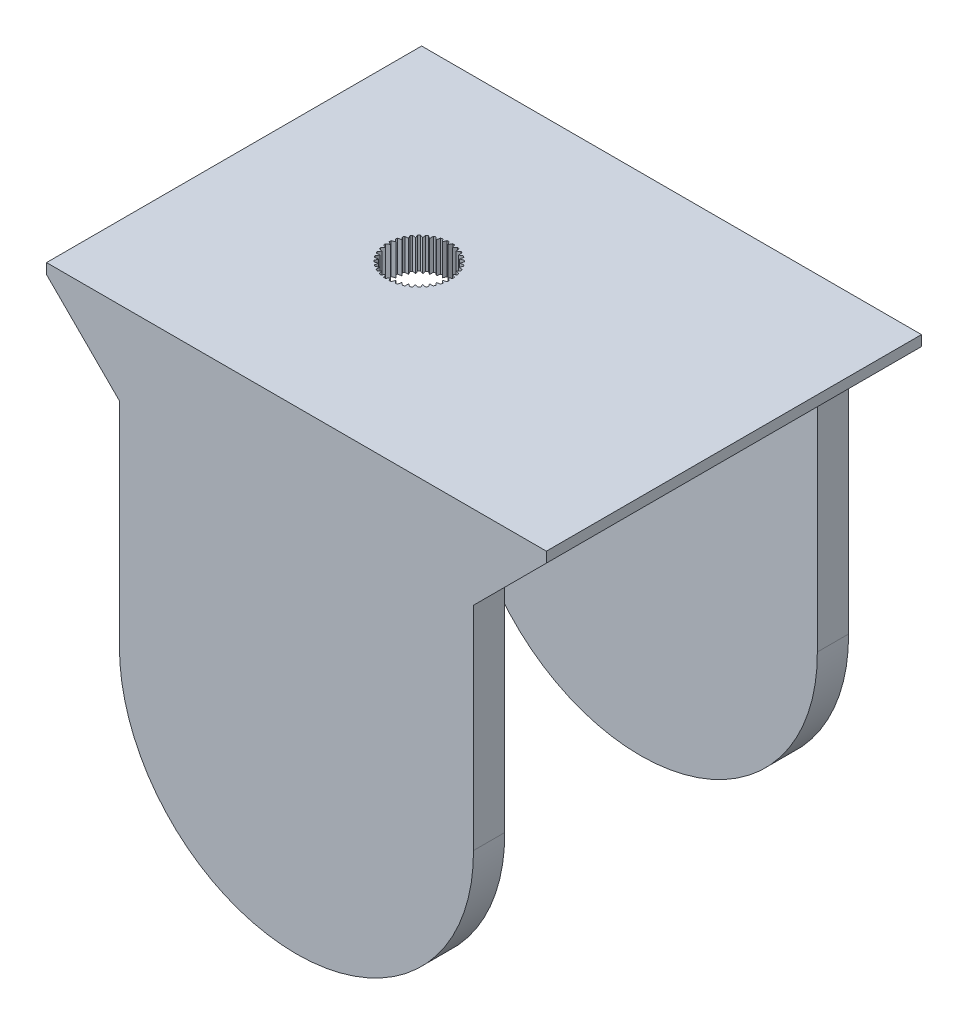
SolidWorks part; units mm, degrees
ref_plane "Front Plane" through (0, 0, 0) normal (0, 0, 1) x (1, 0, 0)
ref_plane "Top Plane" through (0, 0, 0) normal (0, 1, 0) x (1, 0, 0)
ref_plane "Right Plane" through (0, 0, 0) normal (1, 0, 0) x (0, 0, -1)
sketch "Sketch1" plane through (0, 0, 0) normal (0, 1, 0) x (1, 0, 0)
  line L1 (-24, -18.01) -> (24, -18.01)
  line L2 (-24, -18.01) -> (-24, 18.01)
  line L3 (-24, 18.01) -> (24, 18.01)
  line L4 (24, -18.01) -> (24, 18.01)
  point P4 (0, 18.01)
  point P6 (-24, 0)
  dimension "D1" = 48
  dimension "D2" = 36.02
extrude "Boss-Extrude1" add sketch "Sketch1" along normal blind 3
sketch "Sketch2" plane through (0, 3, 0) normal (0, 1, 0) x (1, 0, 0)
  line L0 (2.3718, 1.5412) -> (2.4182, 1.6214) construction
  line L1 (2.3507, 1.7178) -> (2.2594, 1.7017) construction
  line L2 (2.4182, 1.6214) -> (2.4507, 1.6778) construction
  line L3 (2.4148, 1.7291) -> (2.3507, 1.7178) construction
  line L4 (2.2919, 1.4028) -> (2.3718, 1.5412) construction
  line L5 (2.2594, 1.7017) -> (2.1021, 1.6739) construction
  line L6 (2.0999, 2.0167) -> (2.1221, 2.0778) construction
  line L7 (2.0778, 2.1221) -> (2.0167, 2.0999) construction
  line L8 (2.0682, 1.9296) -> (2.0999, 2.0167) construction
  line L9 (2.0167, 2.0999) -> (1.9296, 2.0682) construction
  line L10 (2.0135, 1.7795) -> (2.0682, 1.9296) construction
  line L11 (1.9296, 2.0682) -> (1.7795, 2.0135) construction
  line L12 (1.6778, 2.4507) -> (1.6214, 2.4182) construction
  line L13 (1.7178, 2.3507) -> (1.7291, 2.4148) construction
  line L14 (1.6214, 2.4182) -> (1.5412, 2.3718) construction
  line L15 (1.7017, 2.2594) -> (1.7178, 2.3507) construction
  line L16 (1.5412, 2.3718) -> (1.4028, 2.2919) construction
  line L17 (1.6739, 2.1021) -> (1.7017, 2.2594) construction
  line L18 (2.5007, 0.9835) -> (2.6034, 1.1059) construction
  line L19 (2.5206, 1.2835) -> (2.3608, 1.2835) construction
  line L20 (2.663, 1.1768) -> (2.7048, 1.2267) construction
  line L21 (2.6783, 1.2835) -> (2.6132, 1.2835) construction
  line L22 (2.6034, 1.1059) -> (2.663, 1.1768) construction
  line L23 (2.6132, 1.2835) -> (2.5206, 1.2835) construction
  line L24 (2.8269, 0.6965) -> (2.8767, 0.7384) construction
  line L25 (2.8605, 0.7989) -> (2.7964, 0.8102) construction
  line L26 (2.7559, 0.637) -> (2.8269, 0.6965) construction
  line L27 (2.7964, 0.8102) -> (2.7052, 0.8263) construction
  line L28 (2.6335, 0.5343) -> (2.7559, 0.637) construction
  line L29 (2.7052, 0.8263) -> (2.5478, 0.854) construction
  line L30 (2.6863, 0.0689) -> (2.8247, 0.1488) construction
  line L31 (2.8076, 0.344) -> (2.6574, 0.3986) construction
  line L32 (2.8247, 0.1488) -> (2.9049, 0.1951) construction
  line L33 (2.8946, 0.3123) -> (2.8076, 0.344) construction
  line L34 (2.9049, 0.1951) -> (2.9613, 0.2276) construction
  line L35 (2.9558, 0.29) -> (2.8946, 0.3123) construction
  line L36 (2.9613, -0.2276) -> (2.9049, -0.1951) construction
  line L37 (2.8946, -0.3123) -> (2.9558, -0.29) construction
  line L38 (2.9049, -0.1951) -> (2.8247, -0.1488) construction
  line L39 (2.8076, -0.344) -> (2.8946, -0.3123) construction
  line L40 (2.8247, -0.1488) -> (2.6863, -0.0689) construction
  line L41 (2.6574, -0.3986) -> (2.8076, -0.344) construction
  line L42 (2.7964, -0.8102) -> (2.8605, -0.7989) construction
  line L43 (2.8767, -0.7384) -> (2.8269, -0.6965) construction
  line L44 (2.7052, -0.8263) -> (2.7964, -0.8102) construction
  line L45 (2.8269, -0.6965) -> (2.7559, -0.637) construction
  line L46 (2.5478, -0.854) -> (2.7052, -0.8263) construction
  line L47 (2.7559, -0.637) -> (2.6335, -0.5343) construction
  line L48 (2.5206, -1.2835) -> (2.6132, -1.2835) construction
  line L49 (2.663, -1.1768) -> (2.6034, -1.1059) construction
  line L50 (2.3608, -1.2835) -> (2.5206, -1.2835) construction
  line L51 (2.6034, -1.1059) -> (2.5007, -0.9835) construction
  line L52 (2.6863, -0.0689) -> (2.567, 0) construction
  line L53 (2.567, 0) -> (2.6863, 0.0689) construction
  line L54 (2.6574, 0.3986) -> (2.528, 0.4458) construction
  line L55 (2.528, 0.4458) -> (2.6335, 0.5343) construction
  line L56 (2.5478, 0.854) -> (2.4122, 0.878) construction
  line L57 (2.4122, 0.878) -> (2.5007, 0.9835) construction
  line L58 (2.3608, 1.2835) -> (2.2231, 1.2835) construction
  line L59 (2.2231, 1.2835) -> (2.2919, 1.4028) construction
  line L60 (2.1021, 1.6739) -> (1.9664, 1.65) construction
  line L61 (1.9664, 1.65) -> (2.0135, 1.7795) construction
  line L62 (1.7795, 2.0135) -> (1.65, 1.9664) construction
  line L63 (1.65, 1.9664) -> (1.6739, 2.1021) construction
  line L64 (1.4028, 2.2919) -> (1.2835, 2.2231) construction
  line L65 (1.2835, 2.2231) -> (1.2835, 2.3608) construction
  line L66 (0.9835, 2.5007) -> (0.878, 2.4122) construction
  line L67 (0.878, 2.4122) -> (0.854, 2.5478) construction
  line L68 (0.5343, 2.6335) -> (0.4458, 2.528) construction
  line L69 (0.4458, 2.528) -> (0.3986, 2.6574) construction
  line L70 (0.0689, 2.6863) -> (0, 2.567) construction
  line L71 (0, 2.567) -> (-0.0689, 2.6863) construction
  line L72 (-0.3986, 2.6574) -> (-0.4458, 2.528) construction
  line L73 (-0.4458, 2.528) -> (-0.5343, 2.6335) construction
  line L74 (-0.854, 2.5478) -> (-0.878, 2.4122) construction
  line L75 (-0.878, 2.4122) -> (-0.9835, 2.5007) construction
  line L76 (-1.2835, 2.3608) -> (-1.2835, 2.2231) construction
  line L77 (-1.2835, 2.2231) -> (-1.4028, 2.2919) construction
  line L78 (-1.6739, 2.1021) -> (-1.65, 1.9664) construction
  line L79 (-1.65, 1.9664) -> (-1.7795, 2.0135) construction
  line L80 (-2.0135, 1.7795) -> (-1.9664, 1.65) construction
  line L81 (-1.9664, 1.65) -> (-2.1021, 1.6739) construction
  line L82 (-2.2919, 1.4028) -> (-2.2231, 1.2835) construction
  line L83 (-2.2231, 1.2835) -> (-2.3608, 1.2835) construction
  line L84 (-2.5007, 0.9835) -> (-2.4122, 0.878) construction
  line L85 (-2.4122, 0.878) -> (-2.5478, 0.854) construction
  line L86 (-2.6335, 0.5343) -> (-2.528, 0.4458) construction
  line L87 (-2.528, 0.4458) -> (-2.6574, 0.3986) construction
  line L88 (-2.6863, 0.0689) -> (-2.567, 0) construction
  line L89 (-2.567, 0) -> (-2.6863, -0.0689) construction
  line L90 (-2.6574, -0.3986) -> (-2.528, -0.4458) construction
  line L91 (-2.528, -0.4458) -> (-2.6335, -0.5343) construction
  line L92 (-2.5478, -0.854) -> (-2.4122, -0.878) construction
  line L93 (-2.4122, -0.878) -> (-2.5007, -0.9835) construction
  line L94 (-2.3608, -1.2835) -> (-2.2231, -1.2835) construction
  line L95 (-2.2231, -1.2835) -> (-2.2919, -1.4028) construction
  line L96 (-2.1021, -1.6739) -> (-1.9664, -1.65) construction
  line L97 (-1.9664, -1.65) -> (-2.0135, -1.7795) construction
  line L98 (-1.7795, -2.0135) -> (-1.65, -1.9664) construction
  line L99 (-1.65, -1.9664) -> (-1.6739, -2.1021) construction
  line L100 (-1.4028, -2.2919) -> (-1.2835, -2.2231) construction
  line L101 (-1.2835, -2.2231) -> (-1.2835, -2.3608) construction
  line L102 (-0.9835, -2.5007) -> (-0.878, -2.4122) construction
  line L103 (-0.878, -2.4122) -> (-0.854, -2.5478) construction
  line L104 (-0.5343, -2.6335) -> (-0.4458, -2.528) construction
  line L105 (-0.4458, -2.528) -> (-0.3986, -2.6574) construction
  line L106 (-0.0689, -2.6863) -> (0, -2.567) construction
  line L107 (0, -2.567) -> (0.0689, -2.6863) construction
  line L108 (0.3986, -2.6574) -> (0.4458, -2.528) construction
  line L109 (0.4458, -2.528) -> (0.5343, -2.6335) construction
  line L110 (0.854, -2.5478) -> (0.878, -2.4122) construction
  line L111 (0.878, -2.4122) -> (0.9835, -2.5007) construction
  line L112 (1.2835, -2.3608) -> (1.2835, -2.2231) construction
  line L113 (1.2835, -2.2231) -> (1.4028, -2.2919) construction
  line L114 (1.6739, -2.1021) -> (1.65, -1.9664) construction
  line L115 (1.65, -1.9664) -> (1.7795, -2.0135) construction
  line L116 (2.0135, -1.7795) -> (1.9664, -1.65) construction
  line L117 (1.9664, -1.65) -> (2.1021, -1.6739) construction
  line L118 (2.2919, -1.4028) -> (2.2231, -1.2835) construction
  line L119 (2.2231, -1.2835) -> (2.3608, -1.2835) construction
  line L120 (2.5007, -0.9835) -> (2.4122, -0.878) construction
  line L121 (2.4122, -0.878) -> (2.5478, -0.854) construction
  line L122 (2.6335, -0.5343) -> (2.528, -0.4458) construction
  line L123 (2.528, -0.4458) -> (2.6574, -0.3986) construction
  line L124 (2.6132, -1.2835) -> (2.6783, -1.2835) construction
  line L125 (2.7048, -1.2267) -> (2.663, -1.1768) construction
  line L126 (2.4507, -1.6778) -> (2.4182, -1.6214) construction
  line L127 (2.3507, -1.7178) -> (2.4148, -1.7291) construction
  line L128 (2.4182, -1.6214) -> (2.3718, -1.5412) construction
  line L129 (2.2594, -1.7017) -> (2.3507, -1.7178) construction
  line L130 (1.7795, -2.0135) -> (1.9296, -2.0682) construction
  line L131 (2.0682, -1.9296) -> (2.0135, -1.7795) construction
  line L132 (1.9296, -2.0682) -> (2.0167, -2.0999) construction
  line L133 (2.0999, -2.0167) -> (2.0682, -1.9296) construction
  line L134 (2.0167, -2.0999) -> (2.0778, -2.1221) construction
  line L135 (2.1221, -2.0778) -> (2.0999, -2.0167) construction
  line L136 (2.3718, -1.5412) -> (2.2919, -1.4028) construction
  line L137 (2.1021, -1.6739) -> (2.2594, -1.7017) construction
  line L138 (1.7291, -2.4148) -> (1.7178, -2.3507) construction
  line L139 (1.6214, -2.4182) -> (1.6778, -2.4507) construction
  line L140 (1.7178, -2.3507) -> (1.7017, -2.2594) construction
  line L141 (1.5412, -2.3718) -> (1.6214, -2.4182) construction
  line L142 (1.7017, -2.2594) -> (1.6739, -2.1021) construction
  line L143 (1.4028, -2.2919) -> (1.5412, -2.3718) construction
  line L144 (-0.3123, -2.8946) -> (-0.29, -2.9558) construction
  line L145 (-0.2276, -2.9613) -> (-0.1951, -2.9049) construction
  line L146 (-0.344, -2.8076) -> (-0.3123, -2.8946) construction
  line L147 (-0.1951, -2.9049) -> (-0.1488, -2.8247) construction
  line L148 (0.344, -2.8076) -> (0.3986, -2.6574) construction
  line L149 (0.0689, -2.6863) -> (0.1488, -2.8247) construction
  line L150 (0.3123, -2.8946) -> (0.344, -2.8076) construction
  line L151 (0.1488, -2.8247) -> (0.1951, -2.9049) construction
  line L152 (0.29, -2.9558) -> (0.3123, -2.8946) construction
  line L153 (0.1951, -2.9049) -> (0.2276, -2.9613) construction
  line L154 (0.6965, -2.8269) -> (0.7384, -2.8767) construction
  line L155 (0.7989, -2.8605) -> (0.8102, -2.7964) construction
  line L156 (1.1768, -2.663) -> (1.2267, -2.7048) construction
  line L157 (1.2835, -2.6783) -> (1.2835, -2.6132) construction
  line L158 (1.1059, -2.6034) -> (1.1768, -2.663) construction
  line L159 (1.2835, -2.6132) -> (1.2835, -2.5206) construction
  line L160 (0.9835, -2.5007) -> (1.1059, -2.6034) construction
  line L161 (1.2835, -2.5206) -> (1.2835, -2.3608) construction
  line L162 (0.637, -2.7559) -> (0.6965, -2.8269) construction
  line L163 (0.8102, -2.7964) -> (0.8263, -2.7052) construction
  line L164 (0.5343, -2.6335) -> (0.637, -2.7559) construction
  line L165 (0.8263, -2.7052) -> (0.854, -2.5478) construction
  line L166 (-0.3986, -2.6574) -> (-0.344, -2.8076) construction
  line L167 (-0.1488, -2.8247) -> (-0.0689, -2.6863) construction
  line L168 (-0.8102, -2.7964) -> (-0.7989, -2.8605) construction
  line L169 (-0.7384, -2.8767) -> (-0.6965, -2.8269) construction
  line L170 (-0.8263, -2.7052) -> (-0.8102, -2.7964) construction
  line L171 (-0.6965, -2.8269) -> (-0.637, -2.7559) construction
  line L172 (-0.854, -2.5478) -> (-0.8263, -2.7052) construction
  line L173 (-0.637, -2.7559) -> (-0.5343, -2.6335) construction
  line L174 (-1.2835, -2.6132) -> (-1.2835, -2.6783) construction
  line L175 (-1.2267, -2.7048) -> (-1.1768, -2.663) construction
  line L176 (-1.2835, -2.5206) -> (-1.2835, -2.6132) construction
  line L177 (-1.1768, -2.663) -> (-1.1059, -2.6034) construction
  line L178 (-1.2835, -2.3608) -> (-1.2835, -2.5206) construction
  line L179 (-1.1059, -2.6034) -> (-0.9835, -2.5007) construction
  line L180 (-1.7178, -2.3507) -> (-1.7291, -2.4148) construction
  line L181 (-1.6778, -2.4507) -> (-1.6214, -2.4182) construction
  line L182 (-1.7017, -2.2594) -> (-1.7178, -2.3507) construction
  line L183 (-1.6214, -2.4182) -> (-1.5412, -2.3718) construction
  line L184 (-1.6739, -2.1021) -> (-1.7017, -2.2594) construction
  line L185 (-1.5412, -2.3718) -> (-1.4028, -2.2919) construction
  line L186 (-2.0999, -2.0167) -> (-2.1221, -2.0778) construction
  line L187 (-2.0778, -2.1221) -> (-2.0167, -2.0999) construction
  line L188 (-2.0682, -1.9296) -> (-2.0999, -2.0167) construction
  line L189 (-2.0167, -2.0999) -> (-1.9296, -2.0682) construction
  line L190 (-2.0135, -1.7795) -> (-2.0682, -1.9296) construction
  line L191 (-1.9296, -2.0682) -> (-1.7795, -2.0135) construction
  line L192 (-2.4148, -1.7291) -> (-2.3507, -1.7178) construction
  line L193 (-2.4182, -1.6214) -> (-2.4507, -1.6778) construction
  line L194 (-2.3507, -1.7178) -> (-2.2594, -1.7017) construction
  line L195 (-2.3718, -1.5412) -> (-2.4182, -1.6214) construction
  line L196 (-2.2594, -1.7017) -> (-2.1021, -1.6739) construction
  line L197 (-2.2919, -1.4028) -> (-2.3718, -1.5412) construction
  line L198 (-2.6783, -1.2835) -> (-2.6132, -1.2835) construction
  line L199 (-2.663, -1.1768) -> (-2.7048, -1.2267) construction
  line L200 (-2.6132, -1.2835) -> (-2.5206, -1.2835) construction
  line L201 (-2.6034, -1.1059) -> (-2.663, -1.1768) construction
  line L202 (-2.5206, -1.2835) -> (-2.3608, -1.2835) construction
  line L203 (-2.5007, -0.9835) -> (-2.6034, -1.1059) construction
  line L204 (-2.8605, -0.7989) -> (-2.7964, -0.8102) construction
  line L205 (-2.8269, -0.6965) -> (-2.8767, -0.7384) construction
  line L206 (-2.7964, -0.8102) -> (-2.7052, -0.8263) construction
  line L207 (-2.7559, -0.637) -> (-2.8269, -0.6965) construction
  line L208 (-2.7052, -0.8263) -> (-2.5478, -0.854) construction
  line L209 (-2.6335, -0.5343) -> (-2.7559, -0.637) construction
  line L210 (-2.9558, -0.29) -> (-2.8946, -0.3123) construction
  line L211 (-2.9049, -0.1951) -> (-2.9613, -0.2276) construction
  line L212 (-2.8076, -0.344) -> (-2.6574, -0.3986) construction
  line L213 (-2.6863, -0.0689) -> (-2.8247, -0.1488) construction
  line L214 (-2.8946, -0.3123) -> (-2.8076, -0.344) construction
  line L215 (-2.8247, -0.1488) -> (-2.9049, -0.1951) construction
  line L216 (-2.9613, 0.2276) -> (-2.9049, 0.1951) construction
  line L217 (-2.8946, 0.3123) -> (-2.9558, 0.29) construction
  line L218 (-2.9049, 0.1951) -> (-2.8247, 0.1488) construction
  line L219 (-2.8076, 0.344) -> (-2.8946, 0.3123) construction
  line L220 (-2.8247, 0.1488) -> (-2.6863, 0.0689) construction
  line L221 (-2.6574, 0.3986) -> (-2.8076, 0.344) construction
  line L222 (-2.8269, 0.6965) -> (-2.7559, 0.637) construction
  line L223 (-2.7052, 0.8263) -> (-2.7964, 0.8102) construction
  line L224 (-2.8767, 0.7384) -> (-2.8269, 0.6965) construction
  line L225 (-2.7964, 0.8102) -> (-2.8605, 0.7989) construction
  line L226 (-2.7559, 0.637) -> (-2.6335, 0.5343) construction
  line L227 (-2.5478, 0.854) -> (-2.7052, 0.8263) construction
  line L228 (-2.663, 1.1768) -> (-2.6034, 1.1059) construction
  line L229 (-2.5206, 1.2835) -> (-2.6132, 1.2835) construction
  line L230 (-2.7048, 1.2267) -> (-2.663, 1.1768) construction
  line L231 (-2.6132, 1.2835) -> (-2.6783, 1.2835) construction
  line L232 (-2.6034, 1.1059) -> (-2.5007, 0.9835) construction
  line L233 (-2.3608, 1.2835) -> (-2.5206, 1.2835) construction
  line L234 (-2.4507, 1.6778) -> (-2.4182, 1.6214) construction
  line L235 (-2.3507, 1.7178) -> (-2.4148, 1.7291) construction
  line L236 (-2.4182, 1.6214) -> (-2.3718, 1.5412) construction
  line L237 (-2.2594, 1.7017) -> (-2.3507, 1.7178) construction
  line L238 (-2.3718, 1.5412) -> (-2.2919, 1.4028) construction
  line L239 (-2.1021, 1.6739) -> (-2.2594, 1.7017) construction
  line L240 (-2.0167, 2.0999) -> (-2.0778, 2.1221) construction
  line L241 (-2.1221, 2.0778) -> (-2.0999, 2.0167) construction
  line L242 (-1.9296, 2.0682) -> (-2.0167, 2.0999) construction
  line L243 (-2.0999, 2.0167) -> (-2.0682, 1.9296) construction
  line L244 (-1.7795, 2.0135) -> (-1.9296, 2.0682) construction
  line L245 (-2.0682, 1.9296) -> (-2.0135, 1.7795) construction
  line L246 (-1.7291, 2.4148) -> (-1.7178, 2.3507) construction
  line L247 (-1.6214, 2.4182) -> (-1.6778, 2.4507) construction
  line L248 (-1.7178, 2.3507) -> (-1.7017, 2.2594) construction
  line L249 (-1.5412, 2.3718) -> (-1.6214, 2.4182) construction
  line L250 (-1.7017, 2.2594) -> (-1.6739, 2.1021) construction
  line L251 (-1.4028, 2.2919) -> (-1.5412, 2.3718) construction
  line L252 (-1.2835, 2.6783) -> (-1.2835, 2.6132) construction
  line L253 (-1.1768, 2.663) -> (-1.2267, 2.7048) construction
  line L254 (-1.2835, 2.6132) -> (-1.2835, 2.5206) construction
  line L255 (-1.1059, 2.6034) -> (-1.1768, 2.663) construction
  line L256 (-1.2835, 2.5206) -> (-1.2835, 2.3608) construction
  line L257 (-0.9835, 2.5007) -> (-1.1059, 2.6034) construction
  line L258 (-0.7989, 2.8605) -> (-0.8102, 2.7964) construction
  line L259 (-0.6965, 2.8269) -> (-0.7384, 2.8767) construction
  line L260 (-0.8102, 2.7964) -> (-0.8263, 2.7052) construction
  line L261 (-0.637, 2.7559) -> (-0.6965, 2.8269) construction
  line L262 (-0.8263, 2.7052) -> (-0.854, 2.5478) construction
  line L263 (-0.5343, 2.6335) -> (-0.637, 2.7559) construction
  line L264 (1.1768, 2.663) -> (1.1059, 2.6034) construction
  line L265 (1.2835, 2.5206) -> (1.2835, 2.6132) construction
  line L266 (1.2267, 2.7048) -> (1.1768, 2.663) construction
  line L267 (1.2835, 2.6132) -> (1.2835, 2.6783) construction
  line L268 (1.1059, 2.6034) -> (0.9835, 2.5007) construction
  line L269 (1.2835, 2.3608) -> (1.2835, 2.5206) construction
  line L270 (0.8102, 2.7964) -> (0.7989, 2.8605) construction
  line L271 (0.7384, 2.8767) -> (0.6965, 2.8269) construction
  line L272 (0.8263, 2.7052) -> (0.8102, 2.7964) construction
  line L273 (0.6965, 2.8269) -> (0.637, 2.7559) construction
  line L274 (0.854, 2.5478) -> (0.8263, 2.7052) construction
  line L275 (0.637, 2.7559) -> (0.5343, 2.6335) construction
  line L276 (0.3123, 2.8946) -> (0.29, 2.9558) construction
  line L277 (0.2276, 2.9613) -> (0.1951, 2.9049) construction
  line L278 (0.344, 2.8076) -> (0.3123, 2.8946) construction
  line L279 (0.1951, 2.9049) -> (0.1488, 2.8247) construction
  line L280 (0.3986, 2.6574) -> (0.344, 2.8076) construction
  line L281 (0.1488, 2.8247) -> (0.0689, 2.6863) construction
  line L282 (-0.29, 2.9558) -> (-0.3123, 2.8946) construction
  line L283 (-0.1951, 2.9049) -> (-0.2276, 2.9613) construction
  line L284 (-0.3123, 2.8946) -> (-0.344, 2.8076) construction
  line L285 (-0.1488, 2.8247) -> (-0.1951, 2.9049) construction
  line L286 (-0.344, 2.8076) -> (-0.3986, 2.6574) construction
  line L287 (-0.0689, 2.6863) -> (-0.1488, 2.8247) construction
  line L288 (2.4584, 1.4912) -> (2.5048, 1.5714)
  line L289 (2.5048, 1.5714) -> (2.5684, 1.6817)
  line L290 (2.4587, 1.8384) -> (2.3333, 1.8163)
  line L291 (2.3333, 1.8163) -> (2.2421, 1.8002)
  line L292 (2.2421, 1.8002) -> (2.1196, 1.7786)
  line L293 (2.1196, 1.7786) -> (2.1196, 1.7786)
  line L294 (2.1196, 1.7786) -> (2.1196, 1.7786)
  line L295 (2.1196, 1.7786) -> (2.1622, 1.8954)
  line L296 (2.1622, 1.8954) -> (2.1938, 1.9825)
  line L297 (2.1938, 1.9825) -> (2.2374, 2.1021)
  line L298 (2.1021, 2.2374) -> (1.9825, 2.1938)
  line L299 (1.9825, 2.1938) -> (1.8954, 2.1622)
  line L300 (1.8954, 2.1622) -> (1.7786, 2.1196)
  line L301 (1.7786, 2.1196) -> (1.7786, 2.1196)
  line L302 (1.7786, 2.1196) -> (1.7786, 2.1196)
  line L303 (1.7786, 2.1196) -> (1.8002, 2.2421)
  line L304 (1.8002, 2.2421) -> (1.8163, 2.3333)
  line L305 (1.8163, 2.3333) -> (1.8384, 2.4587)
  line L306 (1.6817, 2.5684) -> (1.5714, 2.5048)
  line L307 (1.5714, 2.5048) -> (1.4912, 2.4584)
  line L308 (1.4912, 2.4584) -> (1.3835, 2.3963)
  line L309 (1.3835, 2.3963) -> (1.3835, 2.3963)
  line L310 (1.3835, 2.3963) -> (1.3835, 2.3963)
  line L311 (1.3835, 2.3963) -> (1.3835, 2.5206)
  line L312 (1.3835, 2.5206) -> (1.3835, 2.6132)
  line L313 (1.3835, 2.6132) -> (1.3835, 2.7406)
  line L314 (1.2101, 2.8214) -> (1.1126, 2.7396)
  line L315 (1.1126, 2.7396) -> (1.0416, 2.68)
  line L316 (1.0416, 2.68) -> (0.9464, 2.6001)
  line L317 (0.9464, 2.6001) -> (0.9464, 2.6001)
  line L318 (0.9464, 2.6001) -> (0.9464, 2.6001)
  line L319 (0.9464, 2.6001) -> (0.9248, 2.7226)
  line L320 (0.9248, 2.7226) -> (0.9087, 2.8138)
  line L321 (0.9087, 2.8138) -> (0.8866, 2.9392)
  line L322 (0.7018, 2.9887) -> (0.6199, 2.8911)
  line L323 (0.6199, 2.8911) -> (0.5604, 2.8202)
  line L324 (0.5604, 2.8202) -> (0.4805, 2.725)
  line L325 (0.4805, 2.725) -> (0.4805, 2.725)
  line L326 (0.4805, 2.725) -> (0.4805, 2.725)
  line L327 (0.4805, 2.725) -> (0.438, 2.8418)
  line L328 (0.438, 2.8418) -> (0.4063, 2.9288)
  line L329 (0.4063, 2.9288) -> (0.3627, 3.0485)
  line L330 (0.1722, 3.0652) -> (0.1085, 2.9549)
  line L331 (0.1085, 2.9549) -> (0.0622, 2.8747)
  line L332 (0.0622, 2.8747) -> (0, 2.767)
  line L333 (0, 2.767) -> (0, 2.767)
  line L334 (0, 2.767) -> (0, 2.767)
  line L335 (0, 2.767) -> (-0.0622, 2.8747)
  line L336 (-0.0622, 2.8747) -> (-0.1085, 2.9549)
  line L337 (-0.1085, 2.9549) -> (-0.1722, 3.0652)
  line L338 (-0.3627, 3.0485) -> (-0.4063, 2.9288)
  line L339 (-0.4063, 2.9288) -> (-0.438, 2.8418)
  line L340 (-0.438, 2.8418) -> (-0.4805, 2.725)
  line L341 (-0.4805, 2.725) -> (-0.4805, 2.725)
  line L342 (-0.4805, 2.725) -> (-0.4805, 2.725)
  line L343 (-0.4805, 2.725) -> (-0.5604, 2.8202)
  line L344 (-0.5604, 2.8202) -> (-0.6199, 2.8911)
  line L345 (-0.6199, 2.8911) -> (-0.7018, 2.9887)
  line L346 (-0.8866, 2.9392) -> (-0.9087, 2.8138)
  line L347 (-0.9087, 2.8138) -> (-0.9248, 2.7226)
  line L348 (-0.9248, 2.7226) -> (-0.9464, 2.6001)
  line L349 (-0.9464, 2.6001) -> (-0.9464, 2.6001)
  line L350 (-0.9464, 2.6001) -> (-0.9464, 2.6001)
  line L351 (-0.9464, 2.6001) -> (-1.0416, 2.68)
  line L352 (-1.0416, 2.68) -> (-1.1126, 2.7396)
  line L353 (-1.1126, 2.7396) -> (-1.2101, 2.8214)
  line L354 (-1.3835, 2.7406) -> (-1.3835, 2.6132)
  line L355 (-1.3835, 2.6132) -> (-1.3835, 2.5206)
  line L356 (-1.3835, 2.5206) -> (-1.3835, 2.3963)
  line L357 (-1.3835, 2.3963) -> (-1.3835, 2.3963)
  line L358 (-1.3835, 2.3963) -> (-1.3835, 2.3963)
  line L359 (-1.3835, 2.3963) -> (-1.4912, 2.4584)
  line L360 (-1.4912, 2.4584) -> (-1.5714, 2.5048)
  line L361 (-1.5714, 2.5048) -> (-1.6817, 2.5684)
  line L362 (-1.8384, 2.4587) -> (-1.8163, 2.3333)
  line L363 (-1.8163, 2.3333) -> (-1.8002, 2.2421)
  line L364 (-1.8002, 2.2421) -> (-1.7786, 2.1196)
  line L365 (-1.7786, 2.1196) -> (-1.7786, 2.1196)
  line L366 (-1.7786, 2.1196) -> (-1.7786, 2.1196)
  line L367 (-1.7786, 2.1196) -> (-1.8954, 2.1622)
  line L368 (-1.8954, 2.1622) -> (-1.9825, 2.1938)
  line L369 (-1.9825, 2.1938) -> (-2.1021, 2.2374)
  line L370 (-2.2374, 2.1021) -> (-2.1938, 1.9825)
  line L371 (-2.1938, 1.9825) -> (-2.1622, 1.8954)
  line L372 (-2.1622, 1.8954) -> (-2.1196, 1.7786)
  line L373 (-2.1196, 1.7786) -> (-2.1196, 1.7786)
  line L374 (-2.1196, 1.7786) -> (-2.1196, 1.7786)
  line L375 (-2.1196, 1.7786) -> (-2.2421, 1.8002)
  line L376 (-2.2421, 1.8002) -> (-2.3333, 1.8163)
  line L377 (-2.3333, 1.8163) -> (-2.4587, 1.8384)
  line L378 (-2.5684, 1.6817) -> (-2.5048, 1.5714)
  line L379 (-2.5048, 1.5714) -> (-2.4584, 1.4912)
  line L380 (-2.4584, 1.4912) -> (-2.3963, 1.3835)
  line L381 (-2.3963, 1.3835) -> (-2.3963, 1.3835)
  line L382 (-2.3963, 1.3835) -> (-2.3963, 1.3835)
  line L383 (-2.3963, 1.3835) -> (-2.5206, 1.3835)
  line L384 (-2.5206, 1.3835) -> (-2.6132, 1.3835)
  line L385 (-2.6132, 1.3835) -> (-2.7406, 1.3835)
  line L386 (-2.8214, 1.2101) -> (-2.7396, 1.1126)
  line L387 (-2.7396, 1.1126) -> (-2.68, 1.0416)
  line L388 (-2.68, 1.0416) -> (-2.6001, 0.9464)
  line L389 (-2.6001, 0.9464) -> (-2.6001, 0.9464)
  line L390 (-2.6001, 0.9464) -> (-2.6001, 0.9464)
  line L391 (-2.6001, 0.9464) -> (-2.7226, 0.9248)
  line L392 (-2.7226, 0.9248) -> (-2.8138, 0.9087)
  line L393 (-2.8138, 0.9087) -> (-2.9392, 0.8866)
  line L394 (-2.9887, 0.7018) -> (-2.8911, 0.6199)
  line L395 (-2.8911, 0.6199) -> (-2.8202, 0.5604)
  line L396 (-2.8202, 0.5604) -> (-2.725, 0.4805)
  line L397 (-2.725, 0.4805) -> (-2.725, 0.4805)
  line L398 (-2.725, 0.4805) -> (-2.725, 0.4805)
  line L399 (-2.725, 0.4805) -> (-2.8418, 0.438)
  line L400 (-2.8418, 0.438) -> (-2.9288, 0.4063)
  line L401 (-2.9288, 0.4063) -> (-3.0485, 0.3627)
  line L402 (-3.0652, 0.1722) -> (-2.9549, 0.1085)
  line L403 (-2.9549, 0.1085) -> (-2.8747, 0.0622)
  line L404 (-2.8747, 0.0622) -> (-2.767, 0)
  line L405 (-2.767, 0) -> (-2.767, 0)
  line L406 (-2.767, 0) -> (-2.767, 0)
  line L407 (-2.767, 0) -> (-2.8747, -0.0622)
  line L408 (-2.8747, -0.0622) -> (-2.9549, -0.1085)
  line L409 (-2.9549, -0.1085) -> (-3.0652, -0.1722)
  line L410 (-3.0485, -0.3627) -> (-2.9288, -0.4063)
  line L411 (-2.9288, -0.4063) -> (-2.8418, -0.438)
  line L412 (-2.8418, -0.438) -> (-2.725, -0.4805)
  line L413 (-2.725, -0.4805) -> (-2.725, -0.4805)
  line L414 (-2.725, -0.4805) -> (-2.725, -0.4805)
  line L415 (-2.725, -0.4805) -> (-2.8202, -0.5604)
  line L416 (-2.8202, -0.5604) -> (-2.8911, -0.6199)
  line L417 (-2.8911, -0.6199) -> (-2.9887, -0.7018)
  line L418 (-2.9392, -0.8866) -> (-2.8138, -0.9087)
  line L419 (-2.8138, -0.9087) -> (-2.7226, -0.9248)
  line L420 (-2.7226, -0.9248) -> (-2.6001, -0.9464)
  line L421 (-2.6001, -0.9464) -> (-2.6001, -0.9464)
  line L422 (-2.6001, -0.9464) -> (-2.6001, -0.9464)
  line L423 (-2.6001, -0.9464) -> (-2.68, -1.0416)
  line L424 (-2.68, -1.0416) -> (-2.7396, -1.1126)
  line L425 (-2.7396, -1.1126) -> (-2.8214, -1.2101)
  line L426 (-2.7406, -1.3835) -> (-2.6132, -1.3835)
  line L427 (-2.6132, -1.3835) -> (-2.5206, -1.3835)
  line L428 (-2.5206, -1.3835) -> (-2.3963, -1.3835)
  line L429 (-2.3963, -1.3835) -> (-2.3963, -1.3835)
  line L430 (-2.3963, -1.3835) -> (-2.3963, -1.3835)
  line L431 (-2.3963, -1.3835) -> (-2.4584, -1.4912)
  line L432 (-2.4584, -1.4912) -> (-2.5048, -1.5714)
  line L433 (-2.5048, -1.5714) -> (-2.5684, -1.6817)
  line L434 (-2.4587, -1.8384) -> (-2.3333, -1.8163)
  line L435 (-2.3333, -1.8163) -> (-2.2421, -1.8002)
  line L436 (-2.2421, -1.8002) -> (-2.1196, -1.7786)
  line L437 (-2.1196, -1.7786) -> (-2.1196, -1.7786)
  line L438 (-2.1196, -1.7786) -> (-2.1196, -1.7786)
  line L439 (-2.1196, -1.7786) -> (-2.1622, -1.8954)
  line L440 (-2.1622, -1.8954) -> (-2.1938, -1.9825)
  line L441 (-2.1938, -1.9825) -> (-2.2374, -2.1021)
  line L442 (-2.1021, -2.2374) -> (-1.9825, -2.1938)
  line L443 (-1.9825, -2.1938) -> (-1.8954, -2.1622)
  line L444 (-1.8954, -2.1622) -> (-1.7786, -2.1196)
  line L445 (-1.7786, -2.1196) -> (-1.7786, -2.1196)
  line L446 (-1.7786, -2.1196) -> (-1.7786, -2.1196)
  line L447 (-1.7786, -2.1196) -> (-1.8002, -2.2421)
  line L448 (-1.8002, -2.2421) -> (-1.8163, -2.3333)
  line L449 (-1.8163, -2.3333) -> (-1.8384, -2.4587)
  line L450 (-1.6817, -2.5684) -> (-1.5714, -2.5048)
  line L451 (-1.5714, -2.5048) -> (-1.4912, -2.4584)
  line L452 (-1.4912, -2.4584) -> (-1.3835, -2.3963)
  line L453 (-1.3835, -2.3963) -> (-1.3835, -2.3963)
  line L454 (-1.3835, -2.3963) -> (-1.3835, -2.3963)
  line L455 (-1.3835, -2.3963) -> (-1.3835, -2.5206)
  line L456 (-1.3835, -2.5206) -> (-1.3835, -2.6132)
  line L457 (-1.3835, -2.6132) -> (-1.3835, -2.7406)
  line L458 (-1.2101, -2.8214) -> (-1.1126, -2.7396)
  line L459 (-1.1126, -2.7396) -> (-1.0416, -2.68)
  line L460 (-1.0416, -2.68) -> (-0.9464, -2.6001)
  line L461 (-0.9464, -2.6001) -> (-0.9464, -2.6001)
  line L462 (-0.9464, -2.6001) -> (-0.9464, -2.6001)
  line L463 (-0.9464, -2.6001) -> (-0.9248, -2.7226)
  line L464 (-0.9248, -2.7226) -> (-0.9087, -2.8138)
  line L465 (-0.9087, -2.8138) -> (-0.8866, -2.9392)
  line L466 (-0.7018, -2.9887) -> (-0.6199, -2.8911)
  line L467 (-0.6199, -2.8911) -> (-0.5604, -2.8202)
  line L468 (-0.5604, -2.8202) -> (-0.4805, -2.725)
  line L469 (-0.4805, -2.725) -> (-0.4805, -2.725)
  line L470 (-0.4805, -2.725) -> (-0.4805, -2.725)
  line L471 (-0.4805, -2.725) -> (-0.438, -2.8418)
  line L472 (-0.438, -2.8418) -> (-0.4063, -2.9288)
  line L473 (-0.4063, -2.9288) -> (-0.3627, -3.0485)
  line L474 (-0.1722, -3.0652) -> (-0.1085, -2.9549)
  line L475 (-0.1085, -2.9549) -> (-0.0622, -2.8747)
  line L476 (-0.0622, -2.8747) -> (0, -2.767)
  line L477 (0, -2.767) -> (0, -2.767)
  line L478 (0, -2.767) -> (0, -2.767)
  line L479 (0, -2.767) -> (0.0622, -2.8747)
  line L480 (0.0622, -2.8747) -> (0.1085, -2.9549)
  line L481 (0.1085, -2.9549) -> (0.1722, -3.0652)
  line L482 (0.3627, -3.0485) -> (0.4063, -2.9288)
  line L483 (0.4063, -2.9288) -> (0.438, -2.8418)
  line L484 (0.438, -2.8418) -> (0.4805, -2.725)
  line L485 (0.4805, -2.725) -> (0.4805, -2.725)
  line L486 (0.4805, -2.725) -> (0.4805, -2.725)
  line L487 (0.4805, -2.725) -> (0.5604, -2.8202)
  line L488 (0.5604, -2.8202) -> (0.6199, -2.8911)
  line L489 (0.6199, -2.8911) -> (0.7018, -2.9887)
  line L490 (0.8866, -2.9392) -> (0.9087, -2.8138)
  line L491 (0.9087, -2.8138) -> (0.9248, -2.7226)
  line L492 (0.9248, -2.7226) -> (0.9464, -2.6001)
  line L493 (0.9464, -2.6001) -> (0.9464, -2.6001)
  line L494 (0.9464, -2.6001) -> (0.9464, -2.6001)
  line L495 (0.9464, -2.6001) -> (1.0416, -2.68)
  line L496 (1.0416, -2.68) -> (1.1126, -2.7396)
  line L497 (1.1126, -2.7396) -> (1.2101, -2.8214)
  line L498 (1.3835, -2.7406) -> (1.3835, -2.6132)
  line L499 (1.3835, -2.6132) -> (1.3835, -2.5206)
  line L500 (1.3835, -2.5206) -> (1.3835, -2.3963)
  line L501 (1.3835, -2.3963) -> (1.3835, -2.3963)
  line L502 (1.3835, -2.3963) -> (1.3835, -2.3963)
  line L503 (1.3835, -2.3963) -> (1.4912, -2.4584)
  line L504 (1.4912, -2.4584) -> (1.5714, -2.5048)
  line L505 (1.5714, -2.5048) -> (1.6817, -2.5684)
  line L506 (1.8384, -2.4587) -> (1.8163, -2.3333)
  line L507 (1.8163, -2.3333) -> (1.8002, -2.2421)
  line L508 (1.8002, -2.2421) -> (1.7786, -2.1196)
  line L509 (1.7786, -2.1196) -> (1.7786, -2.1196)
  line L510 (1.7786, -2.1196) -> (1.7786, -2.1196)
  line L511 (1.7786, -2.1196) -> (1.8954, -2.1622)
  line L512 (1.8954, -2.1622) -> (1.9825, -2.1938)
  line L513 (1.9825, -2.1938) -> (2.1021, -2.2374)
  line L514 (2.2374, -2.1021) -> (2.1938, -1.9825)
  line L515 (2.1938, -1.9825) -> (2.1622, -1.8954)
  line L516 (2.1622, -1.8954) -> (2.1196, -1.7786)
  line L517 (2.1196, -1.7786) -> (2.1196, -1.7786)
  line L518 (2.1196, -1.7786) -> (2.1196, -1.7786)
  line L519 (2.1196, -1.7786) -> (2.2421, -1.8002)
  line L520 (2.2421, -1.8002) -> (2.3333, -1.8163)
  line L521 (2.3333, -1.8163) -> (2.4587, -1.8384)
  line L522 (2.5684, -1.6817) -> (2.5048, -1.5714)
  line L523 (2.5048, -1.5714) -> (2.4584, -1.4912)
  line L524 (2.4584, -1.4912) -> (2.3963, -1.3835)
  line L525 (2.3963, -1.3835) -> (2.3963, -1.3835)
  line L526 (2.3963, -1.3835) -> (2.3963, -1.3835)
  line L527 (2.3963, -1.3835) -> (2.5206, -1.3835)
  line L528 (2.5206, -1.3835) -> (2.6132, -1.3835)
  line L529 (2.6132, -1.3835) -> (2.7406, -1.3835)
  line L530 (2.8214, -1.2101) -> (2.7396, -1.1126)
  line L531 (2.7396, -1.1126) -> (2.68, -1.0416)
  line L532 (2.68, -1.0416) -> (2.6001, -0.9464)
  line L533 (2.6001, -0.9464) -> (2.6001, -0.9464)
  line L534 (2.6001, -0.9464) -> (2.6001, -0.9464)
  line L535 (2.6001, -0.9464) -> (2.7226, -0.9248)
  line L536 (2.7226, -0.9248) -> (2.8138, -0.9087)
  line L537 (2.8138, -0.9087) -> (2.9392, -0.8866)
  line L538 (2.9887, -0.7018) -> (2.8911, -0.6199)
  line L539 (2.8911, -0.6199) -> (2.8202, -0.5604)
  line L540 (2.8202, -0.5604) -> (2.725, -0.4805)
  line L541 (2.725, -0.4805) -> (2.725, -0.4805)
  line L542 (2.725, -0.4805) -> (2.725, -0.4805)
  line L543 (2.725, -0.4805) -> (2.8418, -0.438)
  line L544 (2.8418, -0.438) -> (2.9288, -0.4063)
  line L545 (2.9288, -0.4063) -> (3.0485, -0.3627)
  line L546 (3.0652, -0.1722) -> (2.9549, -0.1085)
  line L547 (2.9549, -0.1085) -> (2.8747, -0.0622)
  line L548 (2.8747, -0.0622) -> (2.767, 0)
  line L549 (2.767, 0) -> (2.767, 0)
  line L550 (2.767, 0) -> (2.767, 0)
  line L551 (2.767, 0) -> (2.8747, 0.0622)
  line L552 (2.8747, 0.0622) -> (2.9549, 0.1085)
  line L553 (2.9549, 0.1085) -> (3.0652, 0.1722)
  line L554 (3.0485, 0.3627) -> (2.9288, 0.4063)
  line L555 (2.9288, 0.4063) -> (2.8418, 0.438)
  line L556 (2.8418, 0.438) -> (2.725, 0.4805)
  line L557 (2.725, 0.4805) -> (2.725, 0.4805)
  line L558 (2.725, 0.4805) -> (2.725, 0.4805)
  line L559 (2.725, 0.4805) -> (2.8202, 0.5604)
  line L560 (2.8202, 0.5604) -> (2.8911, 0.6199)
  line L561 (2.8911, 0.6199) -> (2.9887, 0.7018)
  line L562 (2.9392, 0.8866) -> (2.8138, 0.9087)
  line L563 (2.8138, 0.9087) -> (2.7226, 0.9248)
  line L564 (2.7226, 0.9248) -> (2.6001, 0.9464)
  line L565 (2.6001, 0.9464) -> (2.6001, 0.9464)
  line L566 (2.6001, 0.9464) -> (2.6001, 0.9464)
  line L567 (2.6001, 0.9464) -> (2.68, 1.0416)
  line L568 (2.68, 1.0416) -> (2.7396, 1.1126)
  line L569 (2.7396, 1.1126) -> (2.8214, 1.2101)
  line L570 (2.7406, 1.3835) -> (2.6132, 1.3835)
  line L571 (2.6132, 1.3835) -> (2.5206, 1.3835)
  line L572 (2.5206, 1.3835) -> (2.3963, 1.3835)
  line L573 (2.3963, 1.3835) -> (2.3963, 1.3835)
  line L574 (2.3963, 1.3835) -> (2.3963, 1.3835)
  line L575 (2.3963, 1.3835) -> (2.4584, 1.4912)
  arc A0 (2.4507, 1.6778) -> (2.4148, 1.7291) centre (0, 0) ccw construction
  arc A1 (2.1221, 2.0778) -> (2.0778, 2.1221) centre (0, 0) ccw construction
  arc A2 (1.7291, 2.4148) -> (1.6778, 2.4507) centre (0, 0) ccw construction
  arc A3 (2.7048, 1.2267) -> (2.6783, 1.2835) centre (0, 0) ccw construction
  arc A4 (2.8767, 0.7384) -> (2.8605, 0.7989) centre (0, 0) ccw construction
  arc A5 (2.9613, 0.2276) -> (2.9558, 0.29) centre (0, 0) ccw construction
  arc A6 (2.9558, -0.29) -> (2.9613, -0.2276) centre (0, 0) ccw construction
  arc A7 (2.8605, -0.7989) -> (2.8767, -0.7384) centre (0, 0) ccw construction
  arc A8 (2.6783, -1.2835) -> (2.7048, -1.2267) centre (0, 0) ccw construction
  arc A9 (2.4148, -1.7291) -> (2.4507, -1.6778) centre (0, 0) ccw construction
  arc A10 (2.0778, -2.1221) -> (2.1221, -2.0778) centre (0, 0) ccw construction
  arc A11 (1.6778, -2.4507) -> (1.7291, -2.4148) centre (0, 0) ccw construction
  arc A12 (-0.29, -2.9558) -> (-0.2276, -2.9613) centre (0, 0) ccw construction
  arc A13 (0.2276, -2.9613) -> (0.29, -2.9558) centre (0, 0) ccw construction
  arc A14 (0.7384, -2.8767) -> (0.7989, -2.8605) centre (0, 0) ccw construction
  arc A15 (1.2267, -2.7048) -> (1.2835, -2.6783) centre (0, 0) ccw construction
  arc A16 (-0.7989, -2.8605) -> (-0.7384, -2.8767) centre (0, 0) ccw construction
  arc A17 (-1.2835, -2.6783) -> (-1.2267, -2.7048) centre (0, 0) ccw construction
  arc A18 (-1.7291, -2.4148) -> (-1.6778, -2.4507) centre (0, 0) ccw construction
  arc A19 (-2.1221, -2.0778) -> (-2.0778, -2.1221) centre (0, 0) ccw construction
  arc A20 (-2.4507, -1.6778) -> (-2.4148, -1.7291) centre (0, 0) ccw construction
  arc A21 (-2.7048, -1.2267) -> (-2.6783, -1.2835) centre (0, 0) ccw construction
  arc A22 (-2.8767, -0.7384) -> (-2.8605, -0.7989) centre (0, 0) ccw construction
  arc A23 (-2.9613, -0.2276) -> (-2.9558, -0.29) centre (0, 0) ccw construction
  arc A24 (-2.9558, 0.29) -> (-2.9613, 0.2276) centre (0, 0) ccw construction
  arc A25 (-2.8605, 0.7989) -> (-2.8767, 0.7384) centre (0, 0) ccw construction
  arc A26 (-2.6783, 1.2835) -> (-2.7048, 1.2267) centre (0, 0) ccw construction
  arc A27 (-2.4148, 1.7291) -> (-2.4507, 1.6778) centre (0, 0) ccw construction
  arc A28 (-2.0778, 2.1221) -> (-2.1221, 2.0778) centre (0, 0) ccw construction
  arc A29 (-1.6778, 2.4507) -> (-1.7291, 2.4148) centre (0, 0) ccw construction
  arc A30 (-1.2267, 2.7048) -> (-1.2835, 2.6783) centre (0, 0) ccw construction
  arc A31 (-0.7384, 2.8767) -> (-0.7989, 2.8605) centre (0, 0) ccw construction
  arc A32 (1.2835, 2.6783) -> (1.2267, 2.7048) centre (0, 0) ccw construction
  arc A33 (0.7989, 2.8605) -> (0.7384, 2.8767) centre (0, 0) ccw construction
  arc A34 (0.29, 2.9558) -> (0.2276, 2.9613) centre (0, 0) ccw construction
  arc A35 (-0.2276, 2.9613) -> (-0.29, 2.9558) centre (0, 0) ccw construction
  arc A36 (2.5684, 1.6817) -> (2.4587, 1.8384) centre (0, 0) ccw
  arc A37 (2.2374, 2.1021) -> (2.1021, 2.2374) centre (0, 0) ccw
  arc A38 (1.8384, 2.4587) -> (1.6817, 2.5684) centre (0, 0) ccw
  arc A39 (1.3835, 2.7406) -> (1.2101, 2.8214) centre (0, 0) ccw
  arc A40 (0.8866, 2.9392) -> (0.7018, 2.9887) centre (0, 0) ccw
  arc A41 (0.3627, 3.0485) -> (0.1722, 3.0652) centre (0, 0) ccw
  arc A42 (-0.1722, 3.0652) -> (-0.3627, 3.0485) centre (0, 0) ccw
  arc A43 (-0.7018, 2.9887) -> (-0.8866, 2.9392) centre (0, 0) ccw
  arc A44 (-1.2101, 2.8214) -> (-1.3835, 2.7406) centre (0, 0) ccw
  arc A45 (-1.6817, 2.5684) -> (-1.8384, 2.4587) centre (0, 0) ccw
  arc A46 (-2.1021, 2.2374) -> (-2.2374, 2.1021) centre (0, 0) ccw
  arc A47 (-2.4587, 1.8384) -> (-2.5684, 1.6817) centre (0, 0) ccw
  arc A48 (-2.7406, 1.3835) -> (-2.8214, 1.2101) centre (0, 0) ccw
  arc A49 (-2.9392, 0.8866) -> (-2.9887, 0.7018) centre (0, 0) ccw
  arc A50 (-3.0485, 0.3627) -> (-3.0652, 0.1722) centre (0, 0) ccw
  arc A51 (-3.0652, -0.1722) -> (-3.0485, -0.3627) centre (0, 0) ccw
  arc A52 (-2.9887, -0.7018) -> (-2.9392, -0.8866) centre (0, 0) ccw
  arc A53 (-2.8214, -1.2101) -> (-2.7406, -1.3835) centre (0, 0) ccw
  arc A54 (-2.5684, -1.6817) -> (-2.4587, -1.8384) centre (0, 0) ccw
  arc A55 (-2.2374, -2.1021) -> (-2.1021, -2.2374) centre (0, 0) ccw
  arc A56 (-1.8384, -2.4587) -> (-1.6817, -2.5684) centre (0, 0) ccw
  arc A57 (-1.3835, -2.7406) -> (-1.2101, -2.8214) centre (0, 0) ccw
  arc A58 (-0.8866, -2.9392) -> (-0.7018, -2.9887) centre (0, 0) ccw
  arc A59 (-0.3627, -3.0485) -> (-0.1722, -3.0652) centre (0, 0) ccw
  arc A60 (0.1722, -3.0652) -> (0.3627, -3.0485) centre (0, 0) ccw
  arc A61 (0.7018, -2.9887) -> (0.8866, -2.9392) centre (0, 0) ccw
  arc A62 (1.2101, -2.8214) -> (1.3835, -2.7406) centre (0, 0) ccw
  arc A63 (1.6817, -2.5684) -> (1.8384, -2.4587) centre (0, 0) ccw
  arc A64 (2.1021, -2.2374) -> (2.2374, -2.1021) centre (0, 0) ccw
  arc A65 (2.4587, -1.8384) -> (2.5684, -1.6817) centre (0, 0) ccw
  arc A66 (2.7406, -1.3835) -> (2.8214, -1.2101) centre (0, 0) ccw
  arc A67 (2.9392, -0.8866) -> (2.9887, -0.7018) centre (0, 0) ccw
  arc A68 (3.0485, -0.3627) -> (3.0652, -0.1722) centre (0, 0) ccw
  arc A69 (3.0652, 0.1722) -> (3.0485, 0.3627) centre (0, 0) ccw
  arc A70 (2.9887, 0.7018) -> (2.9392, 0.8866) centre (0, 0) ccw
  arc A71 (2.8214, 1.2101) -> (2.7406, 1.3835) centre (0, 0) ccw
  point P325 (0, 0)
  point P326 (0, 0)
  point P328 (0, 0)
  point P689 (0, 0)
  point P690 (0, 0)
  point P691 (2.8269, 0.6965)
  dimension "D1" = 0.1
extrude "Cut-Extrude1" cut sketch "Sketch2" against normal up to surface (3 mm away) up to face at (0, 0, 0)
sketch "Sketch4" plane through (24, 0, 0) normal (1, 0, 0) x (0, 0, -1)
  line L1 (-18.01, 0) -> (18.01, 0)
  line L2 (-18.01, 0) -> (-18.01, 3)
  line L3 (-18.01, 3) -> (18.01, 3)
  line L4 (18.01, 0) -> (18.01, 3)
extrude "Boss-Extrude3" add sketch "Sketch4" along normal blind 6.23
sketch "Sketch5" plane through (-24, 0, 0) normal (-1, 0, 0) x (0, 0, 1)
  line L1 (-18.01, 0) -> (18.01, 0)
  line L2 (-18.01, 0) -> (-18.01, 3)
  line L3 (-18.01, 3) -> (18.01, 3)
  line L4 (18.01, 0) -> (18.01, 3)
extrude "Cut-Extrude2" cut sketch "Sketch5" against normal blind 6.23
sketch "Sketch6" plane through (0, 0, 0) normal (0, -1, 0) x (1, 0, 0)
  line L0 (-17.77, 18.01) -> (30.23, 18.01) construction
  line L1 (-10.77, 18.01) -> (23.23, 18.01)
  line L2 (-10.77, 18.01) -> (-10.77, 15.01)
  line L3 (-10.77, 15.01) -> (23.23, 15.01)
  line L4 (23.23, 18.01) -> (23.23, 15.01)
  line L5 (-17.77, -18.01) -> (-17.77, 18.01) construction
  line L6 (30.23, 18.01) -> (30.23, -18.01) construction
  line L7 (30.23, -18.01) -> (-17.77, -18.01) construction
  line L8 (-10.77, -15.01) -> (23.23, -15.01)
  line L9 (-10.77, -15.01) -> (-10.77, -18.01)
  line L10 (-10.77, -18.01) -> (23.23, -18.01)
  line L11 (23.23, -15.01) -> (23.23, -18.01)
  dimension "D1" = 3
  dimension "D2" = 7
  dimension "D3" = 7
  dimension "D4" = 3
  dimension "D5" = 7
  dimension "D6" = 7
extrude "Boss-Extrude4" add sketch "Sketch6" along normal blind 25.4
sketch "Sketch7" plane through (0, 0, 18.01) normal (0, 0, 1) x (1, 0, 0)
  line L0 (-10.77, -25.4) -> (23.23, -25.4)
  arc A0 (-10.77, -25.4) -> (23.23, -25.4) centre (6.23, -25.5036) ccw
extrude "Boss-Extrude5" add sketch "Sketch7" against normal up to surface (3 mm away) up to face at (6.23, -12.7, 15.01)
chamfer "Chamfer1" distance 5 angle 45 1 edges at (23.23, 0, 16.51)
chamfer "Chamfer2" distance 5 angle 45 1 edges at (-10.77, 0, 16.51)
sketch "Sketch8" plane through (0, 0, -18.01) normal (0, 0, -1) x (-1, 0, 0)
  line L0 (10.77, -25.4) -> (-23.23, -25.4)
  arc A0 (-23.23, -25.4) -> (10.77, -25.4) centre (-6.23, -25.5056) ccw
extrude "Boss-Extrude6" add sketch "Sketch8" against normal up to surface (3 mm away) up to face at (6.23, -12.7, -15.01)
chamfer "Chamfer3" distance 5 angle 45 2 edges at (-10.77, 0, -16.51) (23.23, 0, -16.51)
chamfer "Chamfer4" distance 2 angle 45 1 edges at (-17.77, 0, 0)
chamfer "Chamfer5" distance 2 angle 45 1 edges at (30.23, 0, 0)
